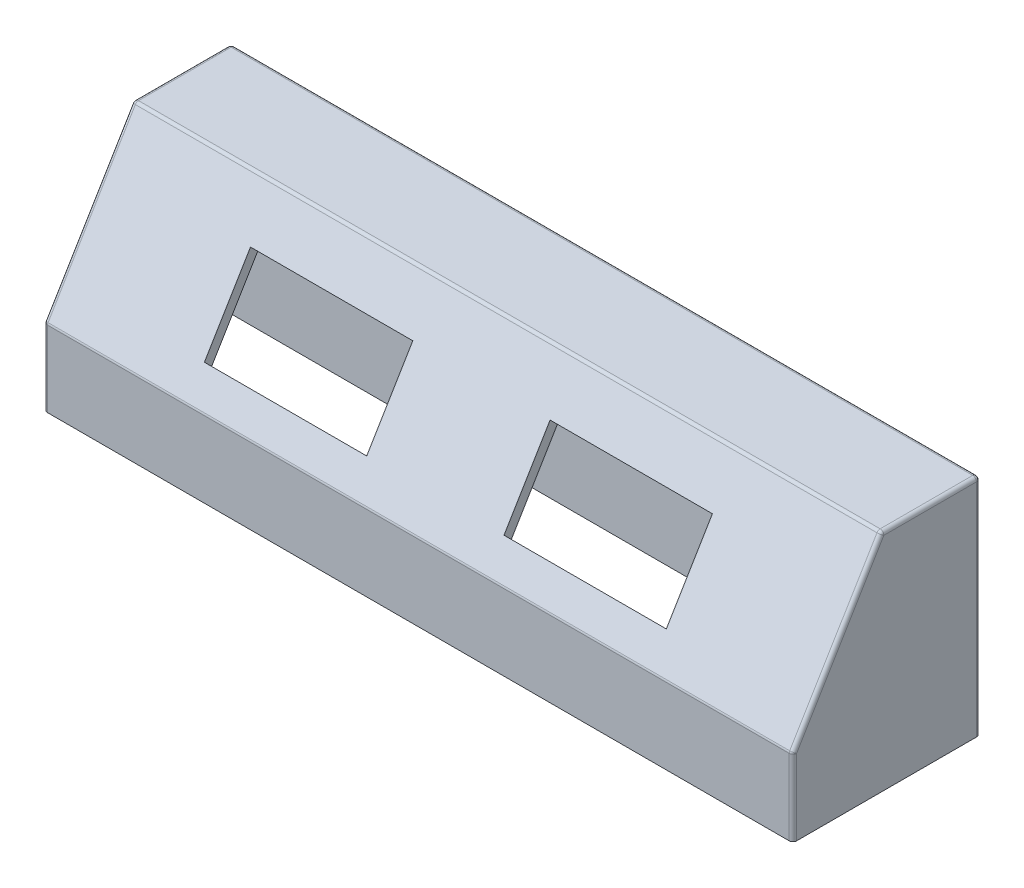
SolidWorks part; units mm, degrees
other "Markup1"
sketch "Sketch7" plane through (57.15, 0, -19.05) normal (0.4749, -0.8524, -0.2189) x (-0.4185, 0, -0.9082)
ref_plane "Front" through (0, 0, 0) normal (0, 0, 1) x (1, 0, 0)
ref_plane "Top" through (0, 0, 0) normal (0, 1, 0) x (1, 0, 0)
ref_plane "Right" through (0, 0, 0) normal (1, 0, 0) x (0, 0, -1)
sketch "Sketch1" plane through (0, 0, 0) normal (0, 1, 0) x (1, 0, 0)
  line L1 (-76.2, 19.05) -> (76.2, 19.05)
  line L2 (-76.2, 19.05) -> (-76.2, -19.05)
  line L3 (-76.2, -19.05) -> (76.2, -19.05)
  line L4 (76.2, 19.05) -> (76.2, -19.05)
  line L5 (-76.2, 19.05) -> (76.2, -19.05) construction
  line L6 (-76.2, -19.05) -> (76.2, 19.05) construction
  point P0 (0, 0)
  dimension "D1" = 38.1
  dimension "D2" = 152.4
extrude "Boss-Extrude1" add sketch "Sketch1" along normal blind 45.72
sketch "Sketch3" plane through (76.2, 0, 0) normal (1, 0, 0) x (0, 0, -1)
  line L0 (-0.9707, 45.72) -> (-19.05, 15.631)
  line L1 (-19.05, 45.72) -> (19.05, 45.72) construction
  line L7 (-19.05, 0) -> (19.05, 0)
  line L8 (19.05, 0) -> (19.05, 45.72)
  line L9 (19.05, 45.72) -> (-19.05, 45.72)
  line L10 (-19.05, 45.72) -> (-19.05, 0)
  line L11 (-19.05, 0) -> (19.05, 0)
  line L12 (19.05, 0) -> (19.05, 45.72)
  line L13 (19.05, 45.72) -> (-19.05, 45.72)
  line L14 (-19.05, 45.72) -> (-19.05, 0)
  line M8 (19.05, 45.72) -> (-19.05, 45.72)
  line M9 (-19.05, 45.72) -> (-19.05, 0)
  dimension "D2" = 59
  dimension "D1" = 0
extrude "Cut-Extrude1" cut sketch "Sketch3" against normal up to next contours L0 M8 M9 region at (76.2, 35.6903, 13.0236)
shell "Shell1" thickness 2.032 removed face at (0, 0, 0)
sketch "Sketch4" plane through (0, 12.5564, 20.8974) normal (0, 0.515, 0.8572) x (1, 0, 0)
  line L0 (0, -20.955) -> (0, 20.955) construction
  line L1 (-46.99, 28.5043) -> (-13.97, 28.5043)
  line L2 (-46.99, 28.5043) -> (-46.99, 11.9943)
  line L3 (-46.99, 11.9943) -> (-13.97, 11.9943)
  line L4 (-13.97, 28.5043) -> (-13.97, 11.9943)
  line L7 (46.99, 11.9943) -> (13.97, 11.9943)
  line L8 (13.97, 28.5043) -> (13.97, 11.9943)
  line L9 (46.99, 28.5043) -> (13.97, 28.5043)
  line L10 (46.99, 28.5043) -> (46.99, 11.9943)
  line L11 (-76.2, 38.6897) -> (0, 38.6897) construction
  line L12 (-76.2, 38.6897) -> (76.2, 38.6897) construction
  line L13 (-76.2, 38.6897) -> (-76.2, 3.5869) construction
  point P0 (-30.48, 28.5043)
  dimension "D1" = 33.02
  dimension "D2" = 16.51
  dimension "D3" = 10.1854
  dimension "D4" = 30.48
extrude "Cut-Extrude2" cut sketch "Sketch4" against normal up to next
fillet "Fillet1" radius 0.762 11 edges at (76.2, 30.6755, 10.0103) (0, 45.72, 0.9707) (-76.2, 30.6755, 10.0103) (0, 15.631, 19.05) (76.2, 7.8155, 19.05) (76.2, 45.72, -9.0397) (-76.2, 45.72, -9.0397) (-76.2, 7.8155, 19.05) (-76.2, 22.86, -19.05) (0, 45.72, -19.05) (76.2, 22.86, -19.05)
chamfer "Chamfer1" distance 5.08 angle 31 2 edges at (30.48, 21.791, 12.9781) (-30.48, 21.791, 12.9781) first distance on face at (-30.48, 28.8669, 8.7264)
